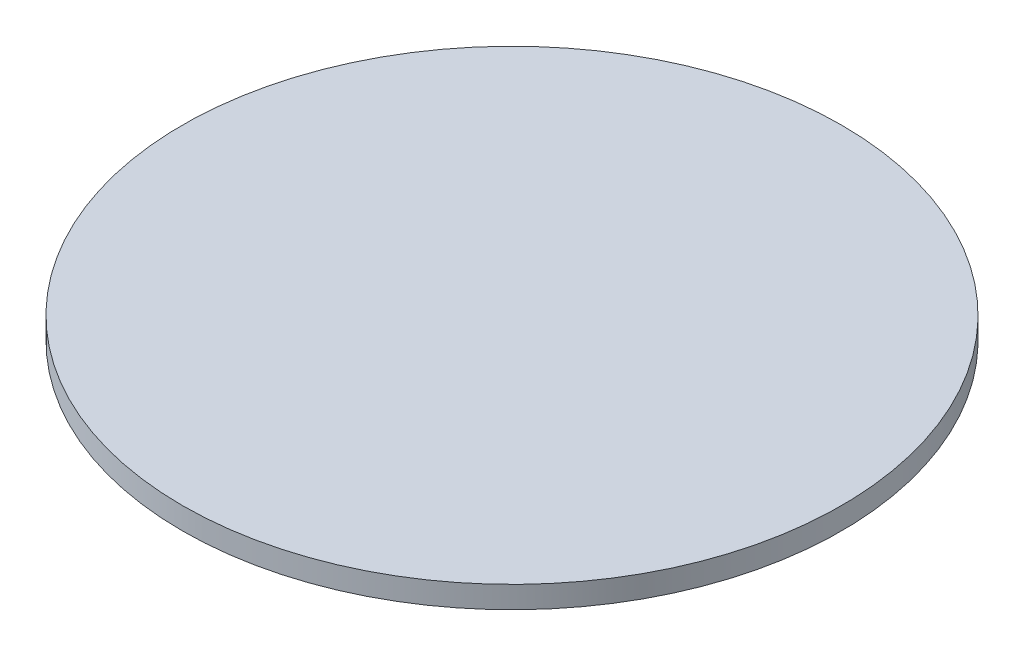
SolidWorks part; units mm, degrees
ref_plane "前视基准面" through (0, 0, 0) normal (0, 0, 1) x (1, 0, 0)
ref_plane "上视基准面" through (0, 0, 0) normal (0, 1, 0) x (1, 0, 0)
ref_plane "右视基准面" through (0, 0, 0) normal (1, 0, 0) x (0, 0, -1)
sketch "草图1" plane through (0, 0, 0) normal (0, 1, 0) x (1, 0, 0)
  circle A0 centre (0, 0) radius 15
  dimension "D1" = 30
extrude "凸台-拉伸1" add sketch "草图1" along normal blind 1
